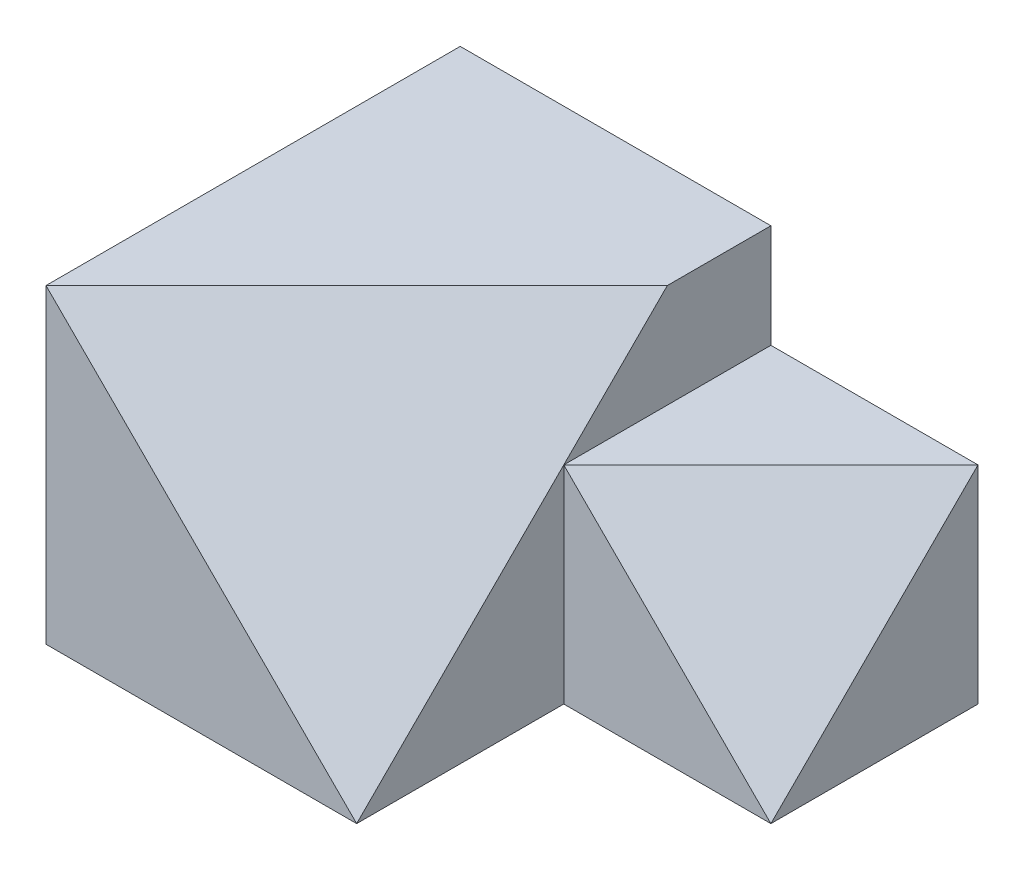
SolidWorks part; units mm, degrees
note: The reader was unsure of these and kept them because the rebuilt part matched: shared geometry of "Sketch1<4>".
ref_plane "Front Plane" through (0, 0, 0) normal (0, 0, 1) x (1, 0, 0)
ref_plane "Top Plane" through (0, 0, 0) normal (0, 1, 0) x (1, 0, 0)
ref_plane "Right Plane" through (0, 0, 0) normal (1, 0, 0) x (0, 0, -1)
sketch "Sketch1" plane through (0, 0, 0) normal (0, 0, 1) x (1, 0, 0)
  line L1 (0, 0) -> (-762, 0)
  line L2 (0, 0) -> (0, 762)
  line L3 (0, 762) -> (-762, 762)
  line L4 (-762, 0) -> (-762, 762)
  line L5 (0, 0) -> (508, 0)
  line L6 (0, 0) -> (0, 508)
  line L7 (0, 508) -> (508, 508)
  line L8 (508, 0) -> (508, 508)
  point P8 (0, 1016)
  dimension "D1" = 762
  dimension "D2" = 508
extrude "Boss-Extrude2" add sketch "Sketch1" along normal blind 1016 contours L4 L1 L2 L3
extrude "Boss-Extrude3" add sketch "Sketch1<4>" along normal blind 508 contours L5 L8 L7 L2
sketch "Sketch1<4>" plane through (0, 0, 0) normal (0, 0, 1) x (1, 0, 0) same geometry as "Sketch1"
ref_plane "Plane1" through (338.6667, 338.6667, 338.6667) normal (0.5774, 0.5774, 0.5774) x (0.8165, -0.4082, -0.4082)
other "SurfaceCut1" flip cut yes
